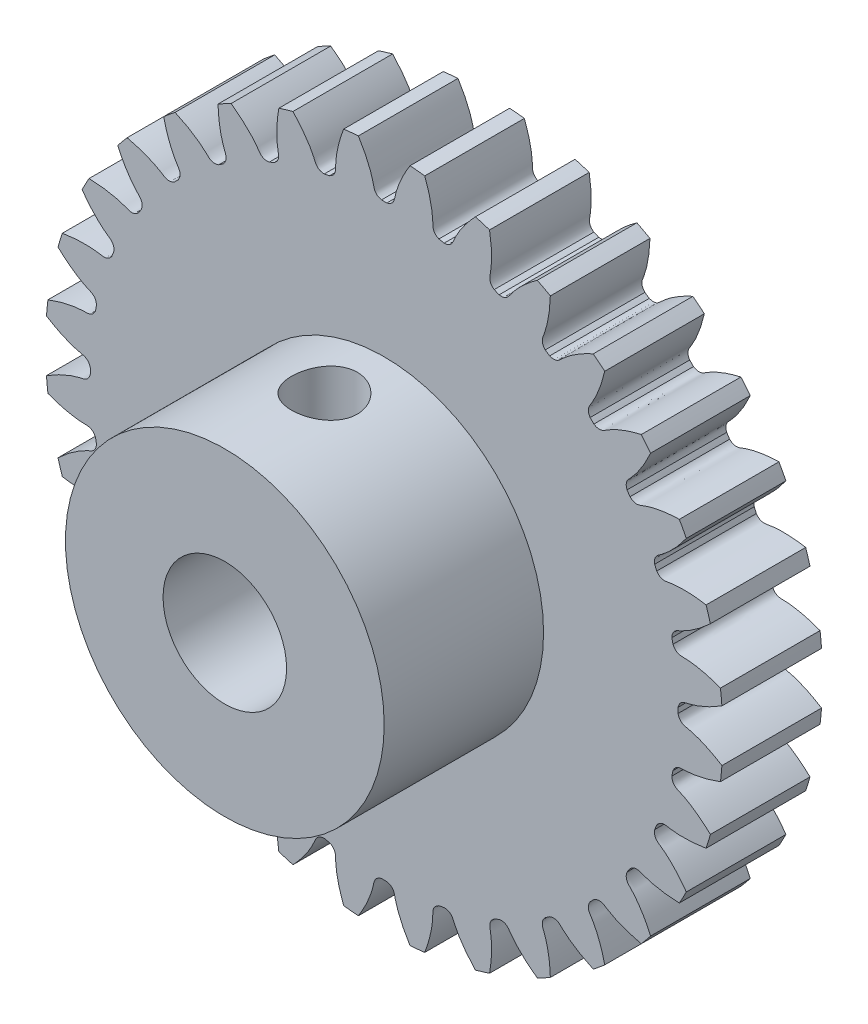
SolidWorks part; units mm, degrees
ref_plane "前视基准面" through (0, 0, 0) normal (0, 0, 1) x (1, 0, 0)
ref_plane "上视基准面" through (0, 0, 0) normal (0, 1, 0) x (1, 0, 0)
ref_plane "右视基准面" through (0, 0, 0) normal (1, 0, 0) x (0, 0, -1)
other "Configuration Table"
sketch "草图1" plane through (0, 0, 0) normal (0, 0, 1) x (1, 0, 0)
  circle A0 centre (0, 0) radius 8.5
extrude "凸台-拉伸1" add sketch "草图1" along normal blind 2.5
ref_axis "基准轴1" through (0, 0, 2.5) along (0, 0, -1)
sketch "草图2" plane through (0, 0, 0) normal (0, 0, 1) x (1, 0, 0)
  line L0 (0, 0) -> (0, 8.5) construction
  circle A0 centre (0, 0) radius 8.5 construction
  arc A1 (0.067, 7.3747) -> (-0.067, 7.3747) centre (0, 0) ccw
  arc A2 (1.6765, 9.6348) -> (-1.6765, 9.6348) centre (0, 0) ccw
  spline S0 degree 3 poles (0.067, 7.3747) (0.2444, 7.4176) (0.2542, 7.5462) (0.2867, 7.6804) (0.2952, 7.7127) (0.3051, 7.7477) (0.3166, 7.7854) (0.3299, 7.8257) (0.3449, 7.8686) (0.3618, 7.9139) (0.3807, 7.9618) (0.4017, 8.012) (0.4249, 8.0645) (0.4505, 8.1193) (0.4785, 8.1763) (0.509, 8.2353) (0.5421, 8.2964) (0.5779, 8.3594) (0.6164, 8.4243) (0.6579, 8.491) (0.7023, 8.5593) (0.7498, 8.6292) (0.8004, 8.7006) (0.8542, 8.7734) (0.9113, 8.8475) (0.9717, 8.9228) (1.0356, 8.9992) (1.1029, 9.0765) (1.1738, 9.1547) (1.2483, 9.2337) (1.3265, 9.3133) (1.4084, 9.3934) (1.5241, 9.5022) (1.6145, 9.5821) (1.6765, 9.6348) knots 0 0 0 0 0.124533 0.135329 0.147193 0.160126 0.174128 0.189198 0.205337 0.222544 0.24082 0.260164 0.280577 0.302059 0.324609 0.348227 0.372914 0.39867 0.425494 0.453386 0.482348 0.512377 0.543476 0.575642 0.608878 0.643181 0.678554 0.714995 0.752504 0.791082 0.830729 0.871444 0.913227 1 1 1 1
  spline S1 degree 3 poles (-0.067, 7.3747) (-0.2444, 7.4176) (-0.2542, 7.5462) (-0.2867, 7.6804) (-0.2952, 7.7127) (-0.3051, 7.7477) (-0.3166, 7.7854) (-0.3299, 7.8257) (-0.3449, 7.8686) (-0.3618, 7.9139) (-0.3807, 7.9618) (-0.4017, 8.012) (-0.4249, 8.0645) (-0.4505, 8.1193) (-0.4785, 8.1763) (-0.509, 8.2353) (-0.5421, 8.2964) (-0.5779, 8.3594) (-0.6164, 8.4243) (-0.6579, 8.491) (-0.7023, 8.5593) (-0.7498, 8.6292) (-0.8004, 8.7006) (-0.8542, 8.7734) (-0.9113, 8.8475) (-0.9717, 8.9228) (-1.0356, 8.9992) (-1.1029, 9.0765) (-1.1738, 9.1547) (-1.2483, 9.2337) (-1.3265, 9.3133) (-1.4084, 9.3934) (-1.5241, 9.5022) (-1.6145, 9.5821) (-1.6765, 9.6348) knots 0 0 0 0 0.124533 0.135329 0.147193 0.160126 0.174128 0.189198 0.205337 0.222544 0.24082 0.260164 0.280577 0.302059 0.324609 0.348227 0.372914 0.39867 0.425494 0.453386 0.482348 0.512377 0.543476 0.575642 0.608878 0.643181 0.678554 0.714995 0.752504 0.791082 0.830729 0.871444 0.913227 1 1 1 1
extrude "切除-拉伸1" cut sketch "草图2" along normal through all
pattern_circular "阵列(圆周)1" count 32 every 11.25 about axis through (0, 0, 2.5) along (0, 0, -1) of "切除-拉伸1"
sketch "草图3" plane through (0, 0, 0) normal (0, 0, 1) x (1, 0, 0)
  circle A0 centre (0, 0) radius 8 construction
  dimension "Dn" = 16
sketch "草图5" plane through (0, 0, 2.5) normal (0, 0, 1) x (1, 0, 0)
  circle A0 centre (0, 0) radius 4
  dimension "D1" = 8
extrude "凸台-拉伸2" add sketch "草图5" along normal blind 4
sketch "草图4" plane through (0, 0, 0) normal (0, 0, -1) x (-1, 0, 0)
  circle A0 centre (0, 0) radius 1.55
  dimension "D1" = 3.1
extrude "切除-拉伸2" cut sketch "草图4" against normal up to next
sketch "草图6" plane through (0, 0, 0) normal (0, 1, 0) x (1, 0, 0)
  line L0 (0, -6.5) -> (0, -2.5) construction
  line L1 (-4, -6.5) -> (4, -6.5) construction
  circle A0 centre (0, -4) radius 0.825
  dimension "D1" = 1.65
  dimension "D2" = 2.5
extrude "切除-拉伸3" cut sketch "草图6" along normal up to next
